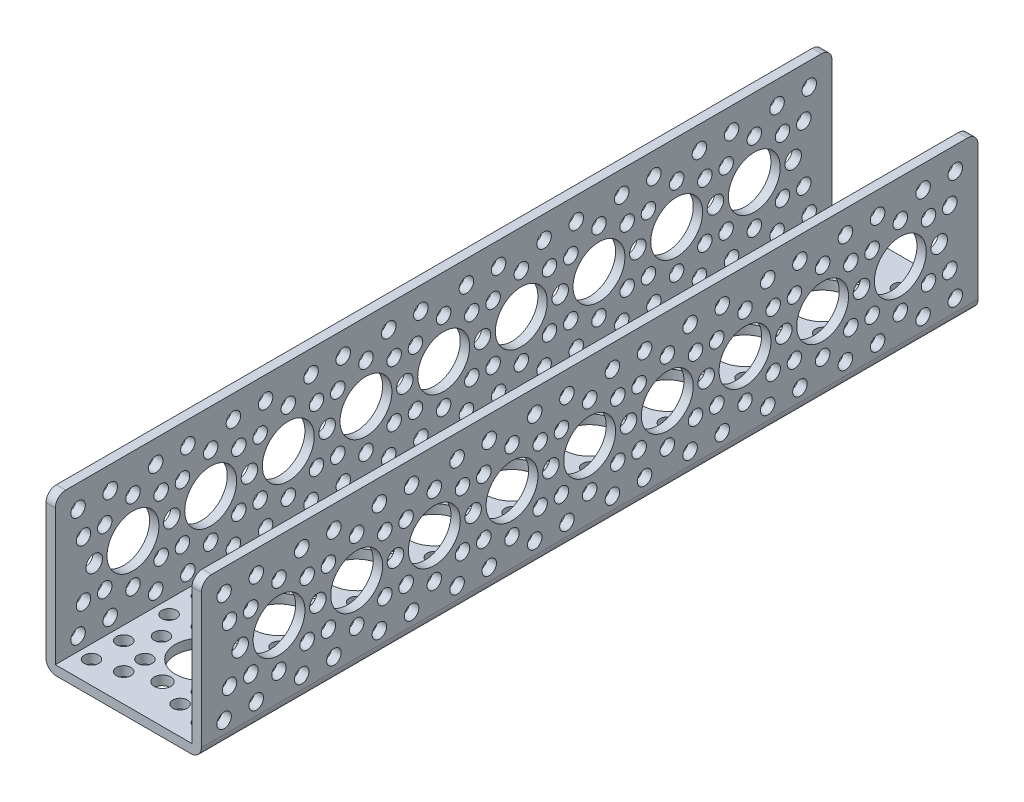
SolidWorks part; units mm, degrees
ref_plane "Front Plane" through (0, 0, 0) normal (0, 0, 1) x (1, 0, 0)
ref_plane "Top Plane" through (0, 0, 0) normal (0, 1, 0) x (1, 0, 0)
ref_plane "Right Plane" through (0, 0, 0) normal (1, 0, 0) x (0, 0, -1)
ref_plane "Plane1" through (0, 0, 0) normal (0, -1, 0) x (1, 0, 0)
sketch "Sketch1" plane through (0, 0, 0) normal (0, -1, 0) x (1, 0, 0)
  line L0 (38.1, 190.5) -> (0, 190.5)
  line L1 (0, 190.5) -> (0, 0)
  line L2 (0, 0) -> (38.1, 0)
  line L3 (38.1, 0) -> (38.1, 190.5)
extrude "Boss-Extrude1" add sketch "Sketch1" against normal blind 38.1
sketch "Sketch2" plane through (0, 0, 190.5) normal (0, 0, 1) x (1, 0, 0)
  line L0 (35.814, 38.1) -> (2.286, 38.1)
  line L1 (2.286, 38.1) -> (2.286, 2.286)
  line L2 (2.286, 2.286) -> (35.814, 2.286)
  line L3 (35.814, 2.286) -> (35.814, 38.1)
extrude "Cut-Extrude1" cut sketch "Sketch2" against normal through all
hole_wizard "Hole1" positions "Sketch4" profile "Sketch3" legacy
sketch "Sketch4" plane through (38.1, 0, 0) normal (1, 0, 0) x (0, 0, -1)
  point P0 (-38.1, 19.05)
  point P1 (-19.05, 19.05)
  point P2 (-57.15, 19.05)
  point P3 (-76.2, 19.05)
  point P4 (-95.25, 19.05)
  point P5 (-114.3, 19.05)
  point P6 (-133.35, 19.05)
  point P7 (-152.4, 19.05)
  point P8 (-171.45, 19.05)
sketch "Sketch3" plane through (38.1, 19.05, 38.1) normal (0, 1, 0) x (0, 0, -1)
  line L0 (0, 0) -> (0, 2.286)
  line L1 (0, 2.286) -> (6.3627, 2.286)
  line L2 (6.3627, 2.286) -> (6.3627, 0)
  line L3 (6.3627, 0) -> (0, 0)
  line L4 (0, 110) -> (0, -10) construction
  dimension "Diameter" = 12.7254
  dimension "Depth" = 2.286
hole_wizard "M3 Clearance Hole1" positions "Sketch6" profile "Sketch5" hole size "M3" standard "ANSI Metric"
sketch "Sketch6" plane through (38.1, 0, 0) normal (1, 0, 0) x (0, 0, -1)
  point P0 (-177.0296, 5.5796)
  point P1 (-183.5852, 12.1352)
  point P2 (-177.0296, 32.5204)
  point P3 (-183.5852, 25.9648)
  point P4 (-13.4704, 5.5796)
  point P5 (-6.9148, 12.1352)
  point P6 (-13.4704, 32.5204)
  point P7 (-6.9148, 25.9648)
  point P8 (-157.9796, 5.5796)
  point P9 (-138.9296, 5.5796)
  point P10 (-119.8796, 5.5796)
  point P11 (-100.8296, 5.5796)
  point P12 (-81.7796, 5.5796)
  point P13 (-62.7296, 5.5796)
  point P14 (-43.6796, 5.5796)
  point P15 (-24.6296, 5.5796)
  point P16 (-157.9796, 32.5204)
  point P17 (-138.9296, 32.5204)
  point P18 (-119.8796, 32.5204)
  point P19 (-100.8296, 32.5204)
  point P20 (-81.7796, 32.5204)
  point P21 (-62.7296, 32.5204)
  point P22 (-43.6796, 32.5204)
  point P23 (-24.6296, 32.5204)
  point P24 (-184.9204, 5.5796)
  point P25 (-184.9204, 32.5204)
  point P26 (-165.8704, 5.5796)
  point P27 (-165.8704, 32.5204)
  point P28 (-146.8204, 5.5796)
  point P29 (-146.8204, 32.5204)
  point P30 (-127.7704, 5.5796)
  point P31 (-127.7704, 32.5204)
  point P32 (-108.7204, 5.5796)
  point P33 (-108.7204, 32.5204)
  point P34 (-89.6704, 5.5796)
  point P35 (-89.6704, 32.5204)
  point P36 (-70.6204, 5.5796)
  point P37 (-70.6204, 32.5204)
  point P38 (-51.5704, 5.5796)
  point P39 (-51.5704, 32.5204)
  point P40 (-38.1, 9.271)
  point P41 (-45.0148, 12.1352)
  point P42 (-45.0148, 25.9648)
  point P43 (-38.1, 28.829)
  point P44 (-31.1852, 25.9648)
  point P45 (-31.1852, 12.1352)
  point P46 (-32.5204, 5.5796)
  point P47 (-32.5204, 32.5204)
  point P48 (-5.5796, 5.5796)
  point P49 (-5.5796, 32.5204)
  point P50 (-12.1352, 12.1352)
  point P51 (-19.05, 9.271)
  point P52 (-25.9648, 12.1352)
  point P53 (-25.9648, 25.9648)
  point P54 (-19.05, 28.829)
  point P55 (-12.1352, 25.9648)
  point P56 (-50.2352, 12.1352)
  point P57 (-69.2852, 12.1352)
  point P58 (-88.3352, 12.1352)
  point P59 (-107.3852, 12.1352)
  point P60 (-126.4352, 12.1352)
  point P61 (-145.4852, 12.1352)
  point P62 (-164.5352, 12.1352)
  point P63 (-50.2352, 25.9648)
  point P64 (-69.2852, 25.9648)
  point P65 (-88.3352, 25.9648)
  point P66 (-107.3852, 25.9648)
  point P67 (-126.4352, 25.9648)
  point P68 (-145.4852, 25.9648)
  point P69 (-164.5352, 25.9648)
  point P70 (-57.15, 28.829)
  point P71 (-76.2, 28.829)
  point P72 (-95.25, 28.829)
  point P73 (-114.3, 28.829)
  point P74 (-133.35, 28.829)
  point P75 (-152.4, 28.829)
  point P76 (-171.45, 28.829)
  point P77 (-64.0648, 25.9648)
  point P78 (-83.1148, 25.9648)
  point P79 (-102.1648, 25.9648)
  point P80 (-121.2148, 25.9648)
  point P81 (-140.2648, 25.9648)
  point P82 (-159.3148, 25.9648)
  point P83 (-178.3648, 25.9648)
  point P84 (-64.0648, 12.1352)
  point P85 (-83.1148, 12.1352)
  point P86 (-102.1648, 12.1352)
  point P87 (-121.2148, 12.1352)
  point P88 (-140.2648, 12.1352)
  point P89 (-159.3148, 12.1352)
  point P90 (-178.3648, 12.1352)
  point P91 (-57.15, 9.271)
  point P92 (-76.2, 9.271)
  point P93 (-95.25, 9.271)
  point P94 (-114.3, 9.271)
  point P95 (-133.35, 9.271)
  point P96 (-152.4, 9.271)
  point P97 (-171.45, 9.271)
sketch "Sketch5" plane through (38.1, 5.5796, 177.0296) normal (0, 1, 0) x (0, 0, -1)
  line L0 (0, 0) -> (0, 2.286)
  line L1 (0, 2.286) -> (1.778, 2.286)
  line L2 (1.778, 2.286) -> (1.778, 0)
  line L5 (1.778, 0) -> (0, 0)
  line L11 (0, -6.35) -> (0, 107.95) construction
  dimension "Thru Hole Dia." = 3.556
  dimension "Thru Hole Depth" = 2.286
hole_wizard "M3.5 Clearance Hole1" positions "Sketch8" profile "Sketch7" hole size "M3.5" standard "ANSI Metric"
sketch "Sketch8" plane through (38.1, 0, 0) normal (1, 0, 0) x (0, 0, -1)
  point P0 (-180.975, 19.05)
  point P1 (-161.925, 19.05)
  point P2 (-142.875, 19.05)
  point P3 (-123.825, 19.05)
  point P4 (-104.775, 19.05)
  point P5 (-85.725, 19.05)
  point P6 (-66.675, 19.05)
  point P7 (-47.625, 19.05)
  point P8 (-28.575, 19.05)
  point P9 (-9.525, 19.05)
sketch "Sketch7" plane through (38.1, 19.05, 180.975) normal (0, 1, 0) x (0, 0, -1)
  line L0 (0, 0) -> (0, 2.286)
  line L1 (0, 2.286) -> (2.032, 2.286)
  line L2 (2.032, 2.286) -> (2.032, 0)
  line L5 (2.032, 0) -> (0, 0)
  line L11 (0, -6.35) -> (0, 107.95) construction
  dimension "Thru Hole Dia." = 4.064
  dimension "Thru Hole Depth" = 2.286
hole_wizard "Hole2" positions "Sketch10" profile "Sketch9" legacy
sketch "Sketch10" plane through (0, 0, 0) normal (0, -1, 0) x (-1, 0, 0)
  point P0 (-19.05, -171.45)
  point P1 (-19.05, -152.4)
  point P2 (-19.05, -133.35)
  point P3 (-19.05, -114.3)
  point P4 (-19.05, -95.25)
  point P5 (-19.05, -76.2)
  point P6 (-19.05, -57.15)
  point P7 (-19.05, -38.1)
  point P8 (-19.05, -19.05)
sketch "Sketch9" plane through (19.05, 0, 171.45) normal (1, 0, 0) x (0, 0, -1)
  line L0 (0, 0) -> (0, 38.1)
  line L1 (0, 38.1) -> (6.3627, 38.1)
  line L2 (6.3627, 38.1) -> (6.3627, 0)
  line L3 (6.3627, 0) -> (0, 0)
  line L4 (0, 110) -> (0, -10) construction
  dimension "Diameter" = 12.7254
  dimension "Depth" = 38.1
hole_wizard "M3.5 Clearance Hole2" positions "Sketch12" profile "Sketch11" hole size "M3.5" standard "ANSI Metric"
sketch "Sketch12" plane through (0, 0, 0) normal (0, -1, 0) x (-1, 0, 0)
  point P0 (-19.05, -180.975)
  point P1 (-19.05, -161.925)
  point P2 (-19.05, -142.875)
  point P3 (-19.05, -123.825)
  point P4 (-19.05, -104.775)
  point P5 (-19.05, -85.725)
  point P6 (-19.05, -66.675)
  point P7 (-19.05, -47.625)
  point P8 (-19.05, -28.575)
  point P9 (-19.05, -9.525)
sketch "Sketch11" plane through (19.05, 0, 180.975) normal (1, 0, 0) x (0, 0, -1)
  line L0 (0, 0) -> (0, 38.1)
  line L1 (0, 38.1) -> (2.032, 38.1)
  line L2 (2.032, 38.1) -> (2.032, 0)
  line L5 (2.032, 0) -> (0, 0)
  line L11 (0, -6.35) -> (0, 107.95) construction
  dimension "Thru Hole Dia." = 4.064
  dimension "Thru Hole Depth" = 38.1
hole_wizard "M3 Clearance Hole2" positions "Sketch14" profile "Sketch13" hole size "M3" standard "ANSI Metric"
sketch "Sketch14" plane through (0, 0, 0) normal (0, -1, 0) x (-1, 0, 0)
  point P0 (-5.5796, -184.9204)
  point P1 (-5.5796, -177.0296)
  point P2 (-12.1352, -183.5852)
  point P3 (-32.5204, -184.9204)
  point P4 (-32.5204, -177.0296)
  point P5 (-25.9648, -183.5852)
  point P6 (-5.5796, -165.8704)
  point P7 (-5.5796, -157.9796)
  point P8 (-32.5204, -165.8704)
  point P9 (-32.5204, -157.9796)
  point P10 (-5.5796, -146.8204)
  point P11 (-5.5796, -138.9296)
  point P12 (-32.5204, -146.8204)
  point P13 (-32.5204, -138.9296)
  point P14 (-5.5796, -127.7704)
  point P15 (-5.5796, -119.8796)
  point P16 (-32.5204, -127.7704)
  point P17 (-32.5204, -119.8796)
  point P18 (-5.5796, -108.7204)
  point P19 (-5.5796, -100.8296)
  point P20 (-32.5204, -108.7204)
  point P21 (-32.5204, -100.8296)
  point P22 (-5.5796, -89.6704)
  point P23 (-5.5796, -81.7796)
  point P24 (-32.5204, -89.6704)
  point P25 (-32.5204, -81.7796)
  point P26 (-5.5796, -70.6204)
  point P27 (-5.5796, -62.7296)
  point P28 (-32.5204, -70.6204)
  point P29 (-32.5204, -62.7296)
  point P30 (-5.5796, -51.5704)
  point P31 (-5.5796, -43.6796)
  point P32 (-32.5204, -51.5704)
  point P33 (-32.5204, -43.6796)
  point P34 (-12.1352, -164.5352)
  point P35 (-9.271, -171.45)
  point P36 (-12.1352, -178.3648)
  point P37 (-25.9648, -178.3648)
  point P38 (-28.829, -171.45)
  point P39 (-25.9648, -164.5352)
  point P40 (-12.1352, -145.4852)
  point P41 (-9.271, -152.4)
  point P42 (-12.1352, -159.3148)
  point P43 (-25.9648, -159.3148)
  point P44 (-28.829, -152.4)
  point P45 (-25.9648, -145.4852)
  point P46 (-12.1352, -126.4352)
  point P47 (-9.271, -133.35)
  point P48 (-12.1352, -140.2648)
  point P49 (-25.9648, -140.2648)
  point P50 (-28.829, -133.35)
  point P51 (-25.9648, -126.4352)
  point P52 (-12.1352, -107.3852)
  point P53 (-9.271, -114.3)
  point P54 (-12.1352, -121.2148)
  point P55 (-25.9648, -121.2148)
  point P56 (-28.829, -114.3)
  point P57 (-25.9648, -107.3852)
  point P58 (-12.1352, -88.3352)
  point P59 (-9.271, -95.25)
  point P60 (-12.1352, -102.1648)
  point P61 (-25.9648, -102.1648)
  point P62 (-28.829, -95.25)
  point P63 (-25.9648, -88.3352)
  point P64 (-12.1352, -69.2852)
  point P65 (-9.271, -76.2)
  point P66 (-12.1352, -83.1148)
  point P67 (-25.9648, -83.1148)
  point P68 (-28.829, -76.2)
  point P69 (-25.9648, -69.2852)
  point P70 (-12.1352, -50.2352)
  point P71 (-9.271, -57.15)
  point P72 (-12.1352, -64.0648)
  point P73 (-25.9648, -64.0648)
  point P74 (-28.829, -57.15)
  point P75 (-25.9648, -50.2352)
  point P76 (-9.271, -38.1)
  point P77 (-12.1352, -45.0148)
  point P78 (-25.9648, -45.0148)
  point P79 (-28.829, -38.1)
  point P80 (-5.5796, -32.5204)
  point P81 (-5.5796, -24.6296)
  point P82 (-12.1352, -31.1852)
  point P83 (-32.5204, -32.5204)
  point P84 (-32.5204, -24.6296)
  point P85 (-25.9648, -31.1852)
  point P86 (-5.5796, -5.5796)
  point P87 (-5.5796, -13.4704)
  point P88 (-12.1352, -6.9148)
  point P89 (-32.5204, -5.5796)
  point P90 (-32.5204, -13.4704)
  point P91 (-25.9648, -6.9148)
  point P92 (-12.1352, -12.1352)
  point P93 (-9.271, -19.05)
  point P94 (-12.1352, -25.9648)
  point P95 (-25.9648, -25.9648)
  point P96 (-28.829, -19.05)
  point P97 (-25.9648, -12.1352)
sketch "Sketch13" plane through (5.5796, 0, 184.9204) normal (1, 0, 0) x (0, 0, -1)
  line L0 (0, 0) -> (0, 38.1)
  line L1 (0, 38.1) -> (1.778, 38.1)
  line L2 (1.778, 38.1) -> (1.778, 0)
  line L5 (1.778, 0) -> (0, 0)
  line L11 (0, -6.35) -> (0, 107.95) construction
  dimension "Thru Hole Dia." = 3.556
  dimension "Thru Hole Depth" = 38.1
hole_wizard "Hole3" positions "Sketch16" profile "Sketch15" legacy
sketch "Sketch16" plane through (0, 0, 0) normal (-1, 0, 0) x (0, 0, 1)
  point P0 (38.1, 19.05)
  point P1 (19.05, 19.05)
  point P2 (57.15, 19.05)
  point P3 (76.2, 19.05)
  point P4 (95.25, 19.05)
  point P5 (114.3, 19.05)
  point P6 (133.35, 19.05)
  point P7 (152.4, 19.05)
  point P8 (171.45, 19.05)
sketch "Sketch15" plane through (0, 19.05, 38.1) normal (0, 1, 0) x (0, 0, 1)
  line L0 (0, 0) -> (0, 38.1)
  line L1 (0, 38.1) -> (6.3627, 38.1)
  line L2 (6.3627, 38.1) -> (6.3627, 0)
  line L3 (6.3627, 0) -> (0, 0)
  line L4 (0, 110) -> (0, -10) construction
  dimension "Diameter" = 12.7254
  dimension "Depth" = 38.1
hole_wizard "M3 Clearance Hole3" positions "Sketch18" profile "Sketch17" hole size "M3" standard "ANSI Metric"
sketch "Sketch18" plane through (0, 0, 0) normal (-1, 0, 0) x (0, 0, 1)
  point P0 (177.0296, 5.5796)
  point P1 (183.5852, 12.1352)
  point P2 (177.0296, 32.5204)
  point P3 (183.5852, 25.9648)
  point P4 (13.4704, 5.5796)
  point P5 (6.9148, 12.1352)
  point P6 (13.4704, 32.5204)
  point P7 (6.9148, 25.9648)
  point P8 (157.9796, 5.5796)
  point P9 (138.9296, 5.5796)
  point P10 (119.8796, 5.5796)
  point P11 (100.8296, 5.5796)
  point P12 (81.7796, 5.5796)
  point P13 (62.7296, 5.5796)
  point P14 (43.6796, 5.5796)
  point P15 (24.6296, 5.5796)
  point P16 (157.9796, 32.5204)
  point P17 (138.9296, 32.5204)
  point P18 (119.8796, 32.5204)
  point P19 (100.8296, 32.5204)
  point P20 (81.7796, 32.5204)
  point P21 (62.7296, 32.5204)
  point P22 (43.6796, 32.5204)
  point P23 (24.6296, 32.5204)
  point P24 (184.9204, 5.5796)
  point P25 (184.9204, 32.5204)
  point P26 (165.8704, 5.5796)
  point P27 (165.8704, 32.5204)
  point P28 (146.8204, 5.5796)
  point P29 (146.8204, 32.5204)
  point P30 (127.7704, 5.5796)
  point P31 (127.7704, 32.5204)
  point P32 (108.7204, 5.5796)
  point P33 (108.7204, 32.5204)
  point P34 (89.6704, 5.5796)
  point P35 (89.6704, 32.5204)
  point P36 (70.6204, 5.5796)
  point P37 (70.6204, 32.5204)
  point P38 (51.5704, 5.5796)
  point P39 (51.5704, 32.5204)
  point P40 (31.1852, 12.1352)
  point P41 (38.1, 9.271)
  point P42 (45.0148, 12.1352)
  point P43 (45.0148, 25.9648)
  point P44 (38.1, 28.829)
  point P45 (31.1852, 25.9648)
  point P46 (32.5204, 5.5796)
  point P47 (32.5204, 32.5204)
  point P48 (5.5796, 5.5796)
  point P49 (5.5796, 32.5204)
  point P50 (12.1352, 12.1352)
  point P51 (19.05, 9.271)
  point P52 (25.9648, 12.1352)
  point P53 (25.9648, 25.9648)
  point P54 (19.05, 28.829)
  point P55 (12.1352, 25.9648)
  point P56 (50.2352, 25.9648)
  point P57 (69.2852, 25.9648)
  point P58 (88.3352, 25.9648)
  point P59 (107.3852, 25.9648)
  point P60 (126.4352, 25.9648)
  point P61 (145.4852, 25.9648)
  point P62 (164.5352, 25.9648)
  point P63 (57.15, 28.829)
  point P64 (76.2, 28.829)
  point P65 (95.25, 28.829)
  point P66 (114.3, 28.829)
  point P67 (133.35, 28.829)
  point P68 (152.4, 28.829)
  point P69 (171.45, 28.829)
  point P70 (64.0648, 25.9648)
  point P71 (83.1148, 25.9648)
  point P72 (102.1648, 25.9648)
  point P73 (121.2148, 25.9648)
  point P74 (140.2648, 25.9648)
  point P75 (159.3148, 25.9648)
  point P76 (178.3648, 25.9648)
  point P77 (64.0648, 12.1352)
  point P78 (83.1148, 12.1352)
  point P79 (102.1648, 12.1352)
  point P80 (121.2148, 12.1352)
  point P81 (140.2648, 12.1352)
  point P82 (159.3148, 12.1352)
  point P83 (178.3648, 12.1352)
  point P84 (57.15, 9.271)
  point P85 (76.2, 9.271)
  point P86 (95.25, 9.271)
  point P87 (114.3, 9.271)
  point P88 (133.35, 9.271)
  point P89 (152.4, 9.271)
  point P90 (171.45, 9.271)
  point P91 (50.2352, 12.1352)
  point P92 (69.2852, 12.1352)
  point P93 (88.3352, 12.1352)
  point P94 (107.3852, 12.1352)
  point P95 (126.4352, 12.1352)
  point P96 (145.4852, 12.1352)
  point P97 (164.5352, 12.1352)
sketch "Sketch17" plane through (0, 5.5796, 177.0296) normal (0, 1, 0) x (0, 0, 1)
  line L0 (0, 0) -> (0, 38.1)
  line L1 (0, 38.1) -> (1.778, 38.1)
  line L2 (1.778, 38.1) -> (1.778, 0)
  line L5 (1.778, 0) -> (0, 0)
  line L11 (0, -6.35) -> (0, 107.95) construction
  dimension "Thru Hole Dia." = 3.556
  dimension "Thru Hole Depth" = 38.1
hole_wizard "M3.5 Clearance Hole3" positions "Sketch20" profile "Sketch19" hole size "M3.5" standard "ANSI Metric"
sketch "Sketch20" plane through (0, 0, 0) normal (-1, 0, 0) x (0, 0, 1)
  point P0 (180.975, 19.05)
  point P1 (161.925, 19.05)
  point P2 (142.875, 19.05)
  point P3 (123.825, 19.05)
  point P4 (104.775, 19.05)
  point P5 (85.725, 19.05)
  point P6 (66.675, 19.05)
  point P7 (47.625, 19.05)
  point P8 (28.575, 19.05)
  point P9 (9.525, 19.05)
sketch "Sketch19" plane through (0, 19.05, 180.975) normal (0, 1, 0) x (0, 0, 1)
  line L0 (0, 0) -> (0, 38.1)
  line L1 (0, 38.1) -> (2.032, 38.1)
  line L2 (2.032, 38.1) -> (2.032, 0)
  line L5 (2.032, 0) -> (0, 0)
  line L11 (0, -6.35) -> (0, 107.95) construction
  dimension "Thru Hole Dia." = 4.064
  dimension "Thru Hole Depth" = 38.1
fillet "Fillet1" radius 2.54 6 edges at (1.143, 38.1, 190.5) (36.957, 38.1, 190.5) (36.957, 38.1, 0) (38.1, 0, 95.25) (1.143, 38.1, 0) (0, 0, 95.25) tangent propagation no
